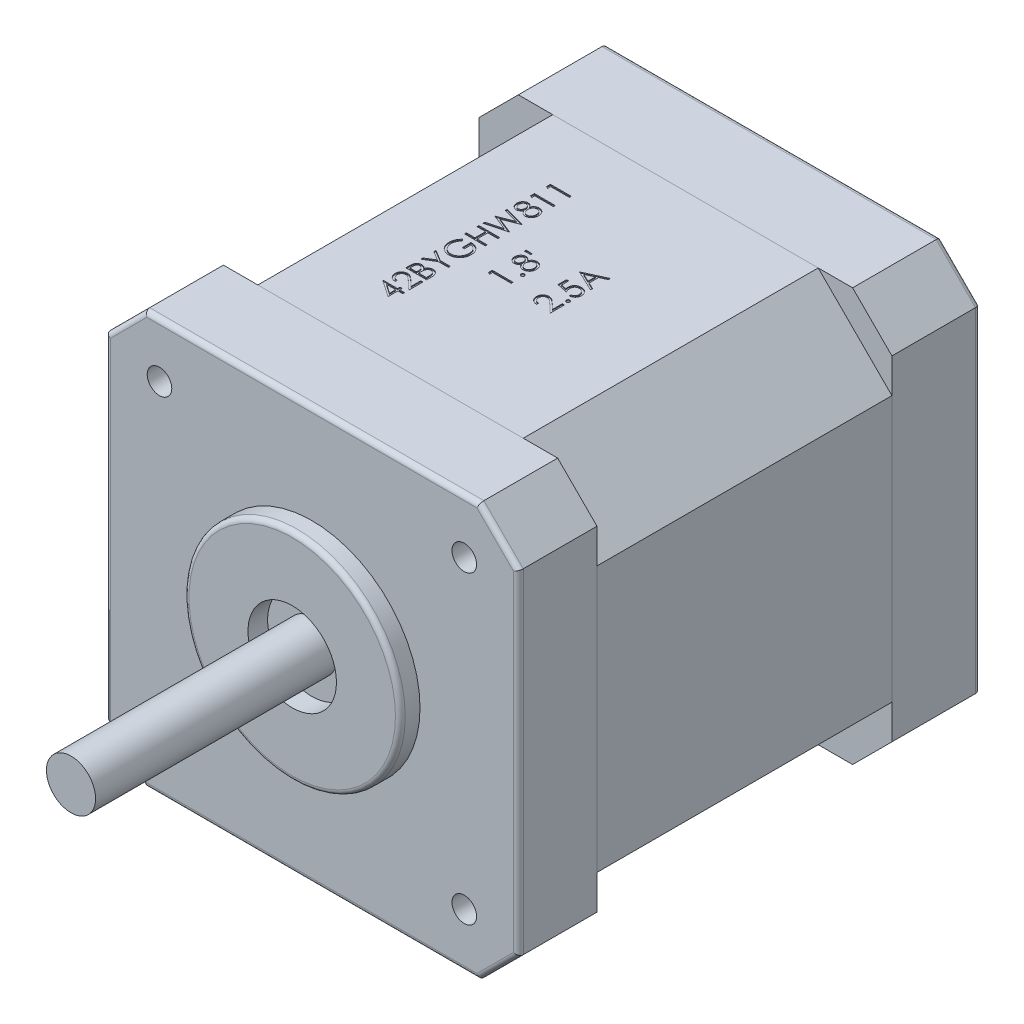
SolidWorks part; units mm, degrees
material "2024-T3"
ref_plane "Ön Düzlem" through (0, 0, 0) normal (0, 0, 1) x (1, 0, 0)
ref_plane "Üst Düzlem" through (0, 0, 0) normal (0, 1, 0) x (1, 0, 0)
ref_plane "Sağ Düzlem" through (0, 0, 0) normal (1, 0, 0) x (0, 0, -1)
sketch "Çizim1" plane through (0, 0, 0) normal (0, 0, 1) x (1, 0, 0)
  line L1 (21, -21) -> (-21, -21)
  line L2 (21, -21) -> (21, 21)
  line L3 (21, 21) -> (-21, 21)
  line L4 (-21, -21) -> (-21, 21)
  line L5 (21, -21) -> (-21, 21) construction
  line L6 (21, 21) -> (-21, -21) construction
  line L7 (15.5, -15.5) -> (-15.5, -15.5) construction
  line L8 (15.5, -15.5) -> (15.5, 15.5) construction
  line L9 (15.5, 15.5) -> (-15.5, 15.5) construction
  line L10 (-15.5, -15.5) -> (-15.5, 15.5) construction
  line L11 (15.5, -15.5) -> (-15.5, 15.5) construction
  line L12 (15.5, 15.5) -> (-15.5, -15.5) construction
  circle A0 centre (0, 0) radius 2.5
  circle A1 centre (0, 0) radius 4.5
  circle A2 centre (0, 0) radius 11
  dimension "D5" = 22
  dimension "D6" = 5
  dimension "D7" = 9
  dimension "D1" = 42
  dimension "D2" = 42
  dimension "D3" = 31
  dimension "D4" = 31
extrude "Yükseklik-Ekstrüzyon1" add sketch "Çizim1" along normal blind 24.5 contours A0 region at (0, 0, 0)
extrude "Yükseklik-Ekstrüzyon2" add sketch "Çizim1<4>" along normal blind 2 separate body contours A2 A1 region at (-10.6889, 0, 0)
sketch "Çizim1<4>" plane through (0, 0, 0) normal (0, 0, 1) x (1, 0, 0) same geometry as "Çizim1"
extrude "Yükseklik-Ekstrüzyon3" add sketch "Çizim1<5>" against normal blind 8 contours L4 L1 L2 L3 A2 | A1 A0 | A0 | A2 A1 region at (0, -20.406, 0) region at (0, 0, 0) region at (-4.3727, 0, 0) region at (-10.6889, 0, 0)
sketch "Çizim1<5>" plane through (0, 0, 0) normal (0, 0, 1) x (1, 0, 0) same geometry as "Çizim1"
chamfer "Pah1" distance 4 angle 45 4 edges at (21, -21, -4) (-21, -21, -4) (-21, 21, -4) (21, 21, -4)
sketch "Çizim2" plane through (0, 0, -8) normal (0, 0, -1) x (-1, 0, 0)
  line L0 (-17, 21) -> (17, 21) construction
  line L1 (-21, -17) -> (-21, 17) construction
  line L2 (21, -17) -> (21, 17) construction
  line L3 (-17, -21) -> (17, -21) construction
  line L4 (-13.5, 21) -> (13.5, 21)
  line L5 (-21, -13.5) -> (-21, 13.5)
  line L6 (21, -13.5) -> (21, 13.5)
  line L7 (-13.5, -21) -> (13.5, -21)
  line L8 (-21, 13.5) -> (-13.5, 21)
  line L9 (21, 13.5) -> (13.5, 21)
  line L10 (13.5, -21) -> (21, -13.5)
  line L11 (-21, -13.5) -> (-13.5, -21)
  point P15 (-21, 21)
  point P17 (21, 21)
  point P19 (21, -21)
  point P21 (-21, -21)
extrude "Yükseklik-Ekstrüzyon4" add sketch "Çizim2" along normal blind 30
sketch "Çizim3" plane through (0, 0, -38) normal (0, 0, -1) x (-1, 0, 0)
  line L8 (-17, -21) -> (17, -21)
  line L9 (-21, -17) -> (-17, -21)
  line L10 (-21, 17) -> (-21, -17)
  line L11 (-17, 21) -> (-21, 17)
  line L12 (17, 21) -> (-17, 21)
  line L13 (21, 17) -> (17, 21)
  line L14 (21, -17) -> (21, 17)
  line L15 (17, -21) -> (21, -17)
  line L16 (-17, -21) -> (17, -21)
  line L17 (-21, -17) -> (-17, -21)
  line L18 (-21, 17) -> (-21, -17)
  line L19 (-17, 21) -> (-21, 17)
  line L20 (17, 21) -> (-17, 21)
  line L21 (21, 17) -> (17, 21)
  line L22 (21, -17) -> (21, 17)
  line L23 (17, -21) -> (21, -17)
  dimension "D1" = 0
extrude "Yükseklik-Ekstrüzyon5" add sketch "Çizim3" along normal blind 9
sketch "Çizim4" plane through (0, 0, -47) normal (0, 0, -1) x (-1, 0, 0)
  circle A0 centre (0, 0) radius 4.5
  dimension "D1" = 9
extrude "Kes-Ekstrüzyon1" cut sketch "Çizim4" against normal blind 3.5
sketch "Çizim5" plane through (21, 0, 0) normal (1, 0, 0) x (0, 0, -1)
  line L0 (8, 13.5) -> (8, 17) construction
  line L1 (8, 31) -> (38, 31)
  line L2 (8, 31) -> (8, -31)
  line L3 (8, -31) -> (38, -31)
  line L4 (38, 31) -> (38, -31)
  line L5 (38, 21) -> (38, 13.5) construction
  line L6 (38, 21) -> (8, 21) construction
  line L7 (47, -21) -> (38, -21) construction
  dimension "D1" = 10
  dimension "D2" = 10
split line "Ayrım Çizgisi1"
hole_wizard "M3 Dişli Delik1" positions "Çizim8" profile "Çizim7" tap size "M3" standard "DIN"
sketch "Çizim8" plane through (0, 0, 0) normal (0, 0, 1) x (1, 0, 0)
  point P0 (-15.5, 15.5)
  point P2 (15.5, 15.5)
  point P4 (15.5, -15.5)
  point P6 (-15.5, -15.5)
sketch "Çizim7" plane through (-15.5, 15.5, 0) normal (1, 0, 0) x (0, -1, 0)
  line L0 (0, 0) -> (0, 7.7511)
  line L1 (0, 7.7511) -> (1.25, 7)
  line L2 (1.25, 7) -> (1.25, 0)
  line L5 (1.25, 0) -> (0, 0)
  line L10 (0, 7.7511) -> (-1.25, 7) construction
  line L11 (0, -6.35) -> (0, 107.95) construction
  dimension "Tap Drill Dia." = 2.5
  dimension "Tap Drill Depth" = 7
  dimension "Drill Angle" = 118
cosmetic thread "Delik Dişi1" parameters "D1"=4.5, "D2"=3
cosmetic thread "Delik Dişi2" parameters "D1"=4.5, "D2"=3
cosmetic thread "Delik Dişi3" parameters "D1"=4.5, "D2"=3
cosmetic thread "Delik Dişi4" parameters "D1"=4.5, "D2"=3
fillet "Radyus1" radius 0.5 1 edges at (11, 0, 2)
fillet "Radyus2" radius 0.5 17 edges at (-4.5, 0, -47) (21, 0, -47) (19, -19, -47) (0, -21, -47) (-19, -19, -47) (-21, 0, -47) (-19, 19, -47) (0, 21, -47) (19, 19, -47) (19, -19, 0) (0, -21, 0) (-19, -19, 0) (-21, 0, 0) (-19, 19, 0) (0, 21, 0) (19, 19, 0) (21, 0, 0)
sketch "Çizim9" plane through (0, 21, 0) normal (0, 1, 0) x (1, 0, 0)
  line L0 (-5.3641, 34.7369) -> (-5.3641, 11.3144) construction
  text T0 "42BYGHW811\r\n1.8' \r\n 2.5A" font "Century Gothic" height in points 8
extrude "Kes-Ekstrüzyon2" cut sketch "Çizim9" against normal blind 0.1
sketch "Çizim11" plane through (0, -21, 0) normal (0, -1, 0) x (1, 0, 0)
  line L0 (-13.5, -38) -> (13.5, -38) construction
  circle A0 centre (-1.5, -39) radius 0.6
  circle A1 centre (1.5, -39) radius 0.6
  circle A2 centre (-1.5, -41) radius 0.6
  circle A3 centre (1.5, -41) radius 0.6
  dimension "D1" = 1.2
  dimension "D2" = 3
  dimension "D3" = 1.5
  dimension "D4" = 1
  dimension "D5" = 2
sketch "Çizim12" plane through (0, 0, 0) normal (1, 0, 0) x (0, 0, -1)
  line L0 (39, -21) -> (39, -26)
  line L1 (38.4, -21) -> (39.6, -21) construction
  line L2 (44, -31) -> (64, -31)
  arc A0 (39, -26) -> (44, -31) centre (44, -26) ccw
  point P7 (39, -31)
  dimension "D3" = 5
  dimension "D1" = 10
  dimension "D2" = 25
sweep "Süpür1" add profiles "Çizim11" path "Çizim12"
